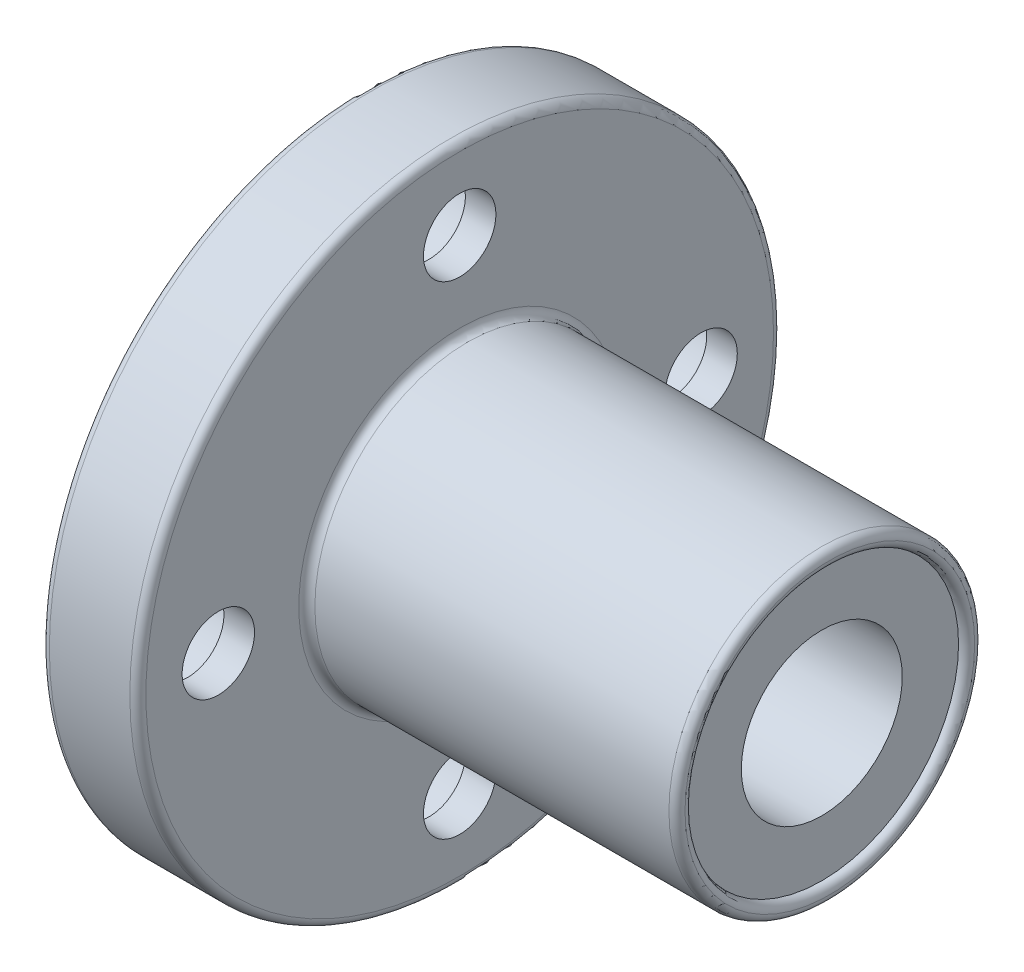
SolidWorks part; units mm, degrees
ref_plane "Ön Düzlem" through (0, 0, 0) normal (0, 0, 1) x (1, 0, 0)
ref_plane "Üst Düzlem" through (0, 0, 0) normal (0, 1, 0) x (1, 0, 0)
ref_plane "Sağ Düzlem" through (0, 0, 0) normal (1, 0, 0) x (0, 0, -1)
sketch "Çizim1" plane through (0, 0, 0) normal (1, 0, 0) x (0, 0, -1)
  circle A0 centre (0, 0) radius 20
  circle A1 centre (0, 0) radius 9.5
  circle A2 centre (0, 0) radius 5
  point P5 (0, 0)
  dimension "D1" = 40
  dimension "D2" = 19
  dimension "D3" = 10
extrude "Yükseklik-Ekstrüzyon1" add sketch "Çizim1" along normal blind 6 contours A0 A1 | A1 A2 region at (0, 0, 19.4343) region at (0, 0, 9.2313)
extrude "Yükseklik-Ekstrüzyon2" add sketch "Çizim1<4>" along normal blind 29 contours A1 | A2
sketch "Çizim1<4>" plane through (0, 0, 0) normal (1, 0, 0) x (0, 0, -1) same geometry as "Çizim1"
sketch "Çizim2" plane through (0, 0, 0) normal (-1, 0, 0) x (0, 0, 1)
  circle A0 centre (0, 15) radius 3.75
  circle A1 centre (0, 15) radius 2.25
  circle A2 centre (15, 0) radius 3.75
  circle A3 centre (15, 0) radius 2.25
  circle A4 centre (0, -15) radius 3.75
  circle A5 centre (0, -15) radius 2.25
  circle A6 centre (-15, 0) radius 3.75
  circle A7 centre (-15, 0) radius 2.25
  point P16 (0, 0)
  dimension "D1" = 7.5
  dimension "D2" = 4.5
  dimension "D3" = 15
  dimension "D4" = 4
extrude "Kes-Ekstrüzyon5" cut sketch "Çizim2" against normal blind 14.1 contours A5 | A3 | A1 | A7
extrude "Kes-Ekstrüzyon6" cut sketch "Çizim2<6>" against normal blind 4.1 contours A5 | A4 | A3 | A2 | A1 | A0 | A7 | A6
sketch "Çizim2<6>" plane through (0, 0, 0) normal (-1, 0, 0) x (0, 0, 1) same geometry as "Çizim2"
sketch "Çizim3" plane through (29, 0, 0) normal (1, 0, 0) x (0, 0, -1)
  circle A0 centre (0, 0) radius 8.5
  dimension "D1" = 17
extrude "Kes-Ekstrüzyon7" cut sketch "Çizim3" against normal blind 0.5
fillet "Radyus1" radius 0.5 5 edges at (0, 0, -20) (6, 0, -20) (6, 0, -9.5) (29, 0, -9.5) (29, 0, -8.5)
ref_plane "Düzlem1" through (14.5, 0, 0) normal (1, 0, 0) x (0, 0, -1)
mirror "Aynalama1" about plane through (14.5, 0, 0) normal (1, 0, 0) of "Kes-Ekstrüzyon7"
